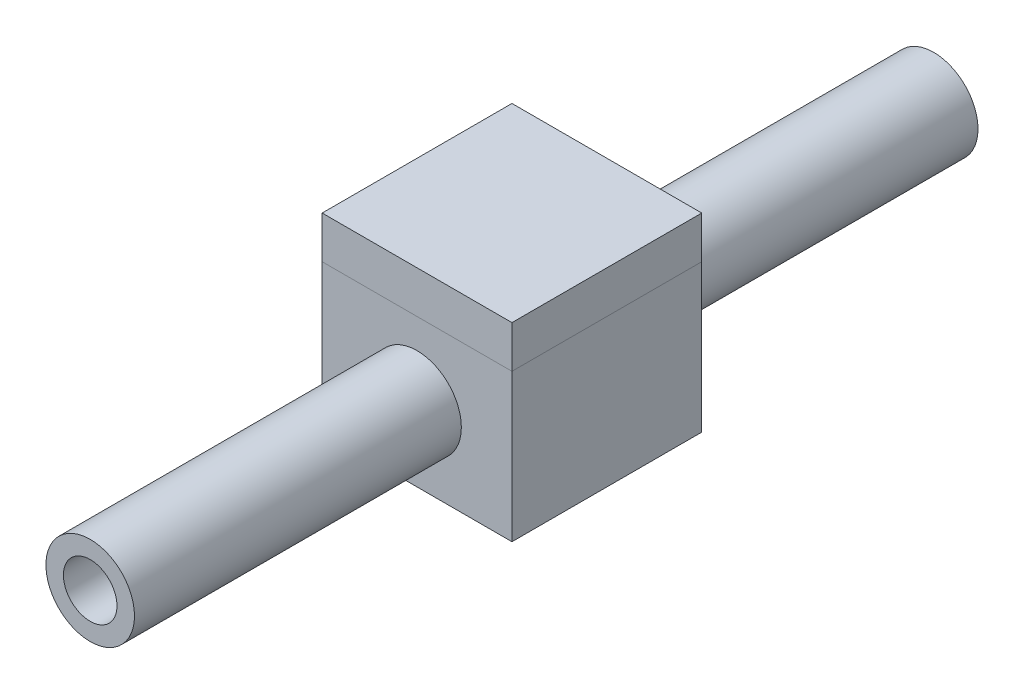
SolidWorks part; units mm, degrees
ref_plane "Front Plane" through (0, 0, 0) normal (0, 0, 1) x (1, 0, 0)
ref_plane "Top Plane" through (0, 0, 0) normal (0, 1, 0) x (1, 0, 0)
ref_plane "Right Plane" through (0, 0, 0) normal (1, 0, 0) x (0, 0, -1)
sketch "Sketch2" plane through (0, 0, 0) normal (0, 0, 1) x (1, 0, 0)
  line L1 (22.5, -17.5) -> (22.5, 27.5)
  line L2 (22.5, 27.5) -> (-22.5, 27.5)
  line L3 (-22.5, 27.5) -> (-22.5, -17.5)
  line L5 (-22.5, 17.5) -> (22.5, 17.5)
  line L6 (-22.5, -17.5) -> (22.5, -17.5)
  dimension "D1" = 10
  dimension "D2" = 35
  dimension "D3" = 45
  dimension "D4" = 22.5
  dimension "D5" = 17.5
extrude "Boss-Extrude1" add sketch "Sketch2" along normal blind 45 contours L3 L6 L1 L5 region at (0, 0, 0)
extrude "Boss-Extrude3" add sketch "Sketch2<4>" along normal blind 45 separate body contours L3 L5 L1 L2 region at (0, 22.5, 0)
sketch "Sketch2<4>" plane through (0, 0, 0) normal (0, 0, 1) x (1, 0, 0) same geometry as "Sketch2"
sketch "Sketch3" plane through (0, 0, 0) normal (0, 0, 1) x (1, 0, 0)
  circle A0 centre (0, 0) radius 6.35
  dimension "D1" = 12.7
extrude "Cut-Extrude2" cut sketch "Sketch3" along normal blind 45
sketch "Sketch5" plane through (0, 0, 0) normal (0, 0, 1) x (1, 0, 0)
  circle A2 centre (0, 0) radius 10.5
  circle A3 centre (0, 0) radius 10.5
  dimension "D1" = 4.15
extrude "Boss-Extrude4" add sketch "Sketch5" against normal blind 77.5
sketch "Sketch6" plane through (0, 0, 0) normal (0, 0, 1) x (1, 0, 0)
  circle A0 centre (0, 0) radius 6.35
  dimension "D1" = 12.7
sketch "Sketch7" plane through (0, 0, 0) normal (0, 0, -1) x (-1, 0, 0)
  circle A0 centre (0, 0) radius 6.35
  dimension "D1" = 12.7
extrude "Cut-Extrude4" cut sketch "Sketch7" along normal blind 77.5
sketch "Sketch8" plane through (0, 0, 45) normal (0, 0, 1) x (1, 0, 0)
  circle A0 centre (0, 0) radius 10.5
  circle A1 centre (0, 0) radius 6.35 construction
  dimension "D1" = 4.15
extrude "Boss-Extrude5" add sketch "Sketch8" along normal blind 77.5
sketch "Sketch9" plane through (0, 0, 122.5) normal (0, 0, 1) x (1, 0, 0)
  circle A0 centre (0, 0) radius 6.35
extrude "Cut-Extrude5" cut sketch "Sketch9" against normal blind 77.5
